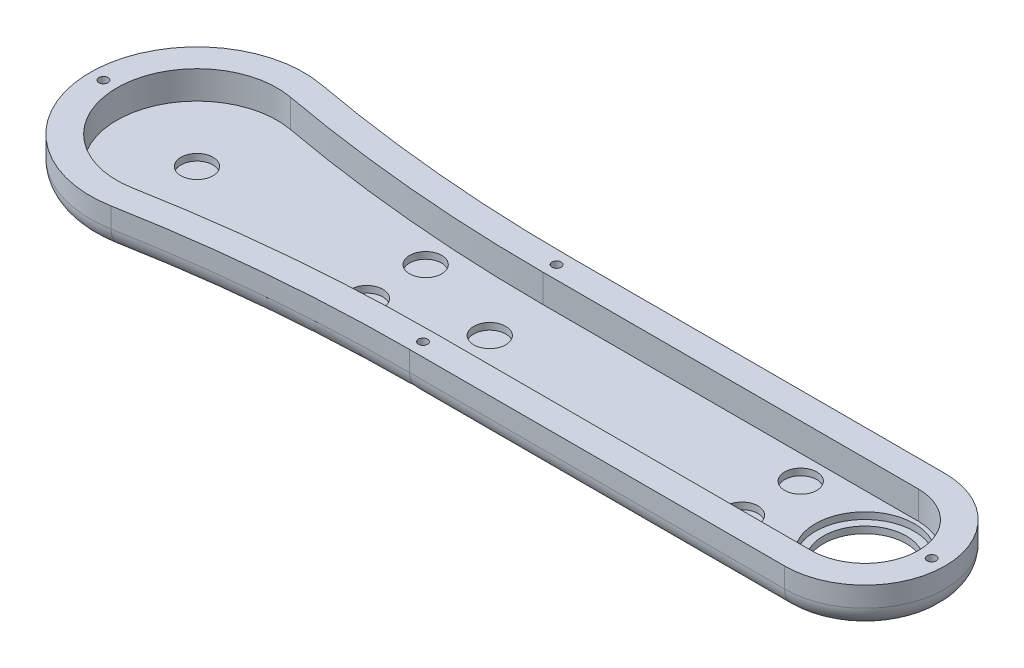
SolidWorks part; units mm, degrees
ref_plane "Front Plane" through (0, 0, 0) normal (0, 0, 1) x (1, 0, 0)
ref_plane "Top Plane" through (0, 0, 0) normal (0, 1, 0) x (1, 0, 0)
ref_plane "Right Plane" through (0, 0, 0) normal (1, 0, 0) x (0, 0, -1)
sketch "Sketch1" plane through (0, 0, 0) normal (0, 1, 0) x (1, 0, 0)
  line L0 (0, 0) -> (250, 0) construction
  line L1 (109.6, 30) -> (109.6, -30) construction
  line L2 (250, 30) -> (109.6, 30)
  line L3 (250, -30) -> (109.6, -30)
  line L4 (109.6, 20) -> (109.6, -20) construction
  line L5 (250, 20) -> (109.6, 20)
  line L6 (250, -20) -> (109.6, -20)
  circle A0 centre (0, 0) radius 30
  circle A1 centre (0, 0) radius 40
  circle A2 centre (109.6, 0) radius 30 construction
  circle A3 centre (250, 0) radius 30
  arc A4 (109.6, 30) -> (7.239, 39.3395) centre (109.6, 595.608) cw
  arc A5 (109.6, -30) -> (7.239, -39.3395) centre (109.6, -595.608) ccw
  circle A6 centre (109.6, 0) radius 20 construction
  circle A7 centre (250, 0) radius 20
  arc A8 (109.6, 20) -> (5.4293, 29.5046) centre (109.6, 595.608) cw
  arc A9 (109.6, -20) -> (5.4293, -29.5046) centre (109.6, -595.608) ccw
  dimension "D1" = 60
  dimension "D2" = 80
  dimension "D4" = 140.4
  dimension "D5" = 60
  dimension "D7" = 40
  dimension "D3" = 250
  dimension "D6" = 109.6
extrude "Boss-Extrude1" add sketch "Sketch1" along normal blind 10.5 contours A1 A9 A0 A8 | A8 L5 A3 L2 A4 A1 | L6 A9 A1 A5 L3 A3 | A7 L6 A3 L5 region at (128.9716, 0, -26.0392) region at (270.6501, 0, -20.6501) region at (19.7576, 0, -33.545) region at (128.9716, 0, 26.0392)
sketch "Sketch4" plane through (0, 0, 0) normal (0, -1, 0) x (1, 0, 0)
  line L0 (250, 30) -> (109.6, 30) construction
  line L1 (250, -30) -> (109.6, -30) construction
  line L2 (250, 30) -> (109.6, 30)
  line L3 (250, -30) -> (109.6, -30)
  circle A0 centre (0, 0) radius 40 construction
  arc A1 (7.239, 39.3395) -> (109.6, 30) centre (109.6, 595.608) ccw construction
  circle A2 centre (250, 0) radius 30 construction
  arc A3 (109.6, -30) -> (7.239, -39.3395) centre (109.6, -595.608) ccw construction
  circle A4 centre (0, 0) radius 40
  arc A5 (7.239, 39.3395) -> (109.6, 30) centre (109.6, 595.608) ccw
  circle A6 centre (250, 0) radius 30
  arc A7 (109.6, -30) -> (7.239, -39.3395) centre (109.6, -595.608) ccw
  circle A8 centre (109.6, 0) radius 6
  circle A9 centre (250, 0) radius 18.5
  circle A10 centre (0, 0) radius 6
  arc M1 (7.239, 39.3395) -> (7.239, -39.3395) centre (0, 0) ccw
  arc M2 (7.239, -39.3395) -> (109.6, -30) centre (109.6, -595.608) cw
  line M3 (109.6, -30) -> (250, -30)
  arc M4 (250, -30) -> (250, 30) centre (250, 0) ccw
  line M5 (250, 30) -> (109.6, 30)
  arc M6 (109.6, 30) -> (7.239, 39.3395) centre (109.6, 595.608) cw
  arc M7 (7.239, 39.3395) -> (7.239, -39.3395) centre (0, 0) ccw
  arc M8 (5.4293, 29.5046) -> (109.6, 20) centre (109.6, 595.608) ccw
  line M9 (109.6, 20) -> (250, 20)
  arc M10 (250, 20) -> (250, -20) centre (250, 0) cw
  line M11 (250, -20) -> (109.6, -20)
  arc M12 (109.6, -20) -> (5.4293, -29.5046) centre (109.6, -595.608) ccw
  arc M27 (5.4293, -29.5046) -> (5.4293, 29.5046) centre (0, 0) cw
  dimension "D1" = 12
  dimension "D2" = 37
  dimension "D3" = 12
extrude "Boss-Extrude4" add sketch "Sketch4" along normal blind 5 contours A6 A4 A8 M9 M8 M12 M11 | A6 A9 M9 M11 M10 | A6 M4 M9 M10 M11 | A6 M5 M6 M7 M8 M9 | A6 M11 M12 M1 M2 M3 | A4 A10 M12 M8 M27 | A4 M7 M12 M27 M8 region at (128.9716, 0, 26.0392) region at (270.6501, 0, 20.6501) region at (238.8197, 0, 19.3597) region at (127.9252, 0, 0) region at (19.7576, 0, 33.545) region at (128.9716, 0, -26.0392) region at (36.7872, 0, 13.1831)
sketch "Sketch6" plane through (0, -5, 0) normal (0, -1, 0) x (1, 0, 0)
  circle A0 centre (109.6, 0) radius 6 construction
  circle A1 centre (109.6, 0) radius 6
  circle A3 centre (0, 0) radius 6 construction
  circle A4 centre (0, 0) radius 6
  circle A5 centre (250, 0) radius 18.5 construction
  circle A6 centre (250, 0) radius 18.5
  circle A7 centre (250, 0) radius 15.5
  dimension "D1" = 31
extrude "Boss-Extrude5" add sketch "Sketch6" against normal blind 2.5
sketch "Sketch8" plane through (0, -5, 0) normal (0, -1, 0) x (-1, 0, 0)
  line L0 (-280, 0) -> (40, 0) construction
  line L1 (-109.6, 30) -> (-109.6, -30) construction
  arc A0 (-250, 30) -> (-250, -30) centre (-250, 0) ccw construction
  arc A1 (-7.239, -39.3395) -> (-7.239, 39.3395) centre (0, 0) ccw construction
hole_wizard "CBORE for M3 Hexagon head bolts-Full thread-grades AB1" positions "3DSketch2" profile "Sketch9" counterbore size "M3" standard "GB" end condition through all
sketch3d "3DSketch2"
  line L0 (280, -5, 0) -> (-40, -5, 0) construction
  line L1 (109.6, -5, -30) -> (109.6, -5, 30) construction
  line L2 (109.6, -5, -30) -> (250, -5, -30) construction
  line L3 (250, -5, 30) -> (109.6, -5, 30) construction
  arc A1 (250, -5, -30) -> (250, -5, 30) centre (250, -5, 0) ccw construction
  arc A2 (7.239, -5, 39.3395) -> (7.239, -5, -39.3395) centre (0, -5, 0) ccw construction
  point P0 (275, -5, 0)
  point P2 (109.6, -5, -25)
  point P4 (-35, -5, 0)
  point P6 (109.6, -5, 25)
  point P24 (250, -35, 0)
  point P32 (0, -45, 0)
  dimension "D4" = 35
  dimension "D1" = 25
  dimension "D2" = 5
  dimension "D3" = 5
sketch "Sketch9" plane through (275, -5, 0) normal (1, 0, 0) x (0, 0, -1)
  line L0 (0, 0) -> (0, 15.5)
  line L1 (0, 15.5) -> (1.7, 15.5)
  line L3 (1.7, 15.5) -> (1.7, 5)
  line L4 (1.7, 5) -> (3.5, 5)
  line L5 (3.5, 5) -> (3.5, 0)
  line L7 (3.5, 0) -> (0, 0)
  line L11 (0, -6.35) -> (0, 107.95) construction
  dimension "Thru Hole Dia." = 3.4
  dimension "Thru Hole Depth" = 15.5
  dimension "C'Bore Dia." = 7
  dimension "C'Bore Depth" = 5
fillet "Fillet1" radius 8 6 edges at (58.2069, -5, -32.3397) (-40, -5, 0) (58.2069, -5, 32.3397) (179.8, -5, 30) (280, -5, 0) (179.8, -5, -30)
sketch "Sketch10" plane through (0, 0, 0) normal (0, 1, 0) x (1, 0, 0)
  line L0 (182.9301, 0) -> (36.2699, 0) construction
  circle A0 centre (74.6, -11) radius 6
  circle A1 centre (74.6, 11) radius 6
  circle A2 centre (215, -11) radius 6
  circle A3 centre (215, 11) radius 6
  circle A4 centre (250, 0) radius 18.5 construction
  circle A5 centre (109.6, 0) radius 6 construction
  point P17 (109.6, 0)
  dimension "D1" = 35
  dimension "D2" = 35
  dimension "D3" = 11
  dimension "D4" = 22
extrude "Cut-Extrude1" cut sketch "Sketch10" against normal blind 2.5
